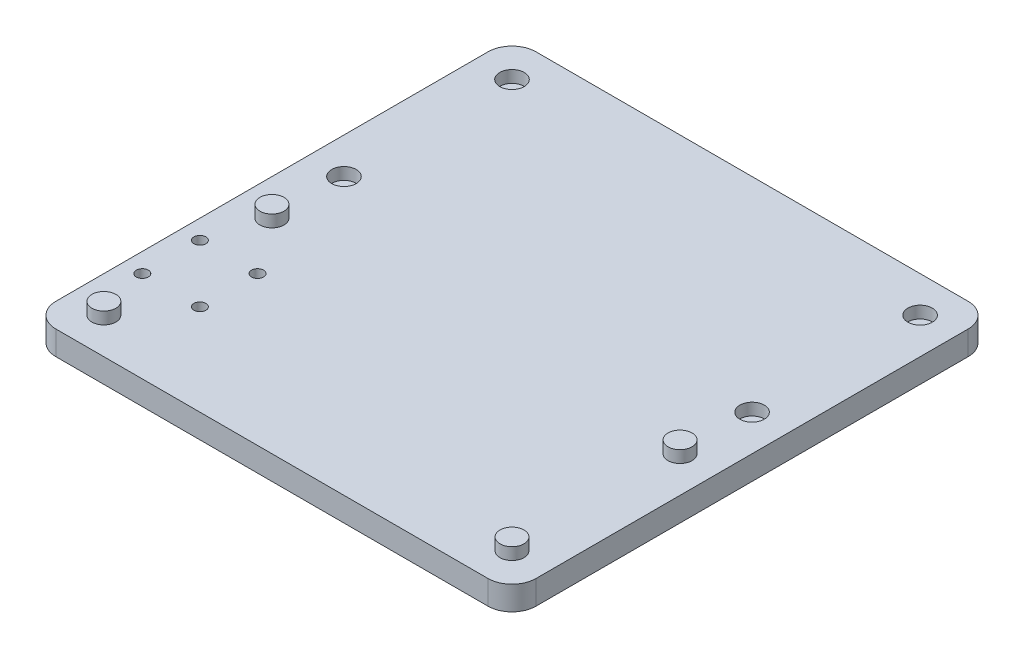
SolidWorks part; units mm, degrees
ref_plane "正面" through (0, 0, 0) normal (0, 0, 1) x (1, 0, 0)
ref_plane "平面" through (0, 0, 0) normal (0, 1, 0) x (1, 0, 0)
ref_plane "右側面" through (0, 0, 0) normal (1, 0, 0) x (0, 0, -1)
sketch "ｽｹｯﾁ1" plane through (0, 0, 0) normal (0, 1, 0) x (1, 0, 0)
  line L1 (-100, -100) -> (100, -100)
  line L2 (-100, -100) -> (-100, 100)
  line L3 (-100, 100) -> (100, 100)
  line L4 (100, -100) -> (100, 100)
  line L5 (-100, -100) -> (100, 100) construction
  line L6 (-100, 100) -> (100, -100) construction
  point P0 (0, 0)
  dimension "D1" = 200
  dimension "D2" = 200
extrude "ﾎﾞｽ - 押し出し1" add sketch "ｽｹｯﾁ1" along normal blind 10
sketch "ｽｹｯﾁ2" plane through (0, 10, 0) normal (0, 1, 0) x (1, 0, 0)
  line L19 (-100, 100) -> (-100, -100) construction
  line L20 (100, -100) -> (100, 100) construction
  line L21 (-100, -100) -> (100, -100) construction
  circle A0 centre (-85, -15) radius 5
  circle A1 centre (-85, -85) radius 5
  circle A2 centre (85, -85) radius 5
  circle A3 centre (85, -15) radius 5
  dimension "D1" = 10
  dimension "D2" = 15
  dimension "D3" = 15
  dimension "D4" = 15
  dimension "D5" = 15
extrude "ﾎﾞｽ - 押し出し2" add sketch "ｽｹｯﾁ2" along normal blind 5
fillet "ﾌｨﾚｯﾄ1" radius 10 4 edges at (100, 5, -100) (100, 5, 100) (-100, 5, 100) (-100, 5, -100)
sketch "ｽｹｯﾁ3" plane through (0, 10, 0) normal (0, 1, 0) x (1, 0, 0)
  line L0 (90, 100) -> (-90, 100) construction
  line L1 (-100, 90) -> (-100, -90) construction
  line L2 (100, -90) -> (100, 90) construction
  circle A0 centre (-85, 85) radius 5.1
  circle A1 centre (85, 85) radius 5.1
  circle A2 centre (-85, 15) radius 5.1
  circle A3 centre (85, 15) radius 5.1
  dimension "D1" = 10.2
  dimension "D2" = 15
  dimension "D3" = 15
  dimension "D4" = 15
  dimension "D5" = 15
extrude "ｶｯﾄ - 押し出し1" cut sketch "ｽｹｯﾁ3" against normal blind 5
sketch "ｽｹｯﾁ4" plane through (0, 10, 0) normal (0, 1, 0) x (1, 0, 0)
  line L0 (-85, -20) -> (-85, -80) construction
  line L2 (-85, -50) -> (-80, -50) construction
  line L3 (-100, 90) -> (-100, -90) construction
  circle A1 centre (-85, -15) radius 5 construction
  circle A2 centre (-85, -15) radius 5 construction
  circle A3 centre (-85, -85) radius 5 construction
  circle A4 centre (-68, -38) radius 2.5
  circle A5 centre (-68, -62) radius 2.5
  circle A6 centre (-92, -62) radius 2.5
  circle A7 centre (-92, -38) radius 2.5
  point P22 (0, 0)
  point P23 (0, 0)
  point P24 (0, 0)
  point P25 (0, 0)
  dimension "D2" = 24
  dimension "D3" = 24
  dimension "D6" = 5
  dimension "D1" = 20
  dimension "D4" = 12
  dimension "D5" = 12
extrude "ｶｯﾄ - 押し出し2" cut sketch "ｽｹｯﾁ4" against normal through all
